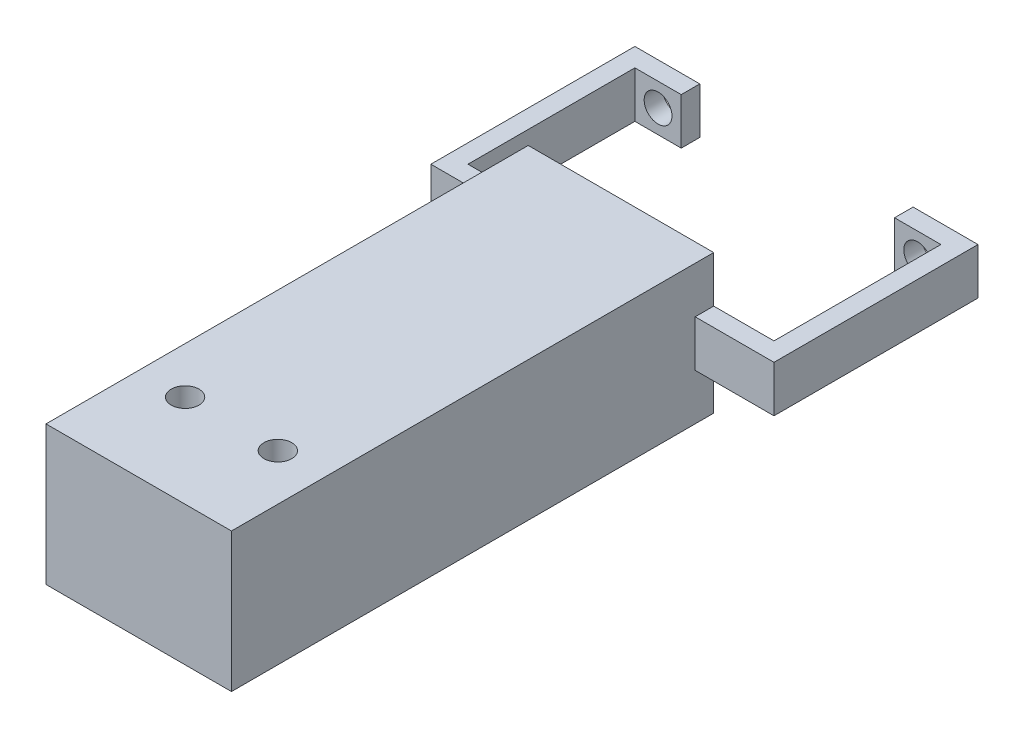
SolidWorks part; units mm, degrees
ref_plane "Спереди" through (0, 0, 0) normal (0, 0, 1) x (1, 0, 0)
ref_plane "Сверху" through (0, 0, 0) normal (0, 1, 0) x (1, 0, 0)
ref_plane "Справа" through (0, 0, 0) normal (1, 0, 0) x (0, 0, -1)
sketch "Эскиз1" plane through (0, 0, 0) normal (0, 0, 1) x (1, 0, 0)
  line L3 (11.5, 0) -> (11.5, 2.5)
  line L4 (11.5, 2.5) -> (16.5, 2.5)
  line L7 (11.5, -2.5) -> (11.5, 0)
  line L8 (11.5, -2.5) -> (16.5, -2.5)
  line L14 (-16.5, 2.5) -> (-18.5, 2.5)
  line L15 (-11.5, 0) -> (-11.5, 2.5)
  line L16 (-11.5, 2.5) -> (-16.5, 2.5)
  line L18 (-16.5, -2.5) -> (-11.5, -2.5)
  line L19 (-11.5, -2.5) -> (-11.5, 0)
  line L20 (-18.5, 2.5) -> (-18.5, -2.5)
  line L21 (-18.5, -2.5) -> (-16.5, -2.5)
  line L22 (16.5, -2.5) -> (18.5, -2.5)
  line L23 (18.5, -2.5) -> (18.5, 2.5)
  line L24 (18.5, 2.5) -> (16.5, 2.5)
  circle A0 centre (14, 0) radius 1.5
  circle A1 centre (-14, 0) radius 1.5
extrude "Бобышка-Вытянуть1" add sketch "Эскиз1" along normal blind 2
sketch "Эскиз3" plane through (0, 0, 2) normal (0, 0, 1) x (1, 0, 0)
  line L0 (-18.5, 2.5) -> (-16.5, 2.5)
  line L1 (-11.5, 2.5) -> (-18.5, 2.5) construction
  line L2 (-16.5, 2.5) -> (-16.5, -2.5)
  line L3 (-18.5, -2.5) -> (-11.5, -2.5) construction
  line L4 (-16.5, -2.5) -> (-18.5, -2.5)
  line L5 (-18.5, -2.5) -> (-18.5, 2.5)
  line L6 (18.5, -2.5) -> (16.5, -2.5)
  line L7 (11.5, -2.5) -> (18.5, -2.5) construction
  line L8 (16.5, -2.5) -> (16.5, 2.5)
  line L9 (18.5, 2.5) -> (11.5, 2.5) construction
  line L10 (16.5, 2.5) -> (18.5, 2.5)
  line L11 (18.5, 2.5) -> (18.5, -2.5)
extrude "Бобышка-Вытянуть2" add sketch "Эскиз3" along normal blind 18
sketch "Эскиз4" plane through (18.5, 0, 0) normal (1, 0, 0) x (0, 0, -1)
  line L0 (-20, -2.5) -> (-22, -2.5)
  line L1 (-22, -2.5) -> (-22, 2.5)
  line L2 (-22, 2.5) -> (-20, 2.5)
  line L3 (-20, -2.5) -> (-20, 2.5) construction
  line L4 (-20, 2.5) -> (-20, -2.5)
extrude "Бобышка-Вытянуть3" add sketch "Эскиз4" against normal blind 37
sketch "Эскиз5" plane through (0, 0, 22) normal (0, 0, 1) x (1, 0, 0)
  line L1 (-18.5, 2.5) -> (18.5, 2.5) construction
  line L2 (-10, 2.5) -> (-10, 7.5)
  line L3 (-10, 7.5) -> (10, 7.5)
  line L4 (10, 7.5) -> (10, -7.5)
  line L5 (10, -7.5) -> (-10, -7.5)
  line L6 (-10, -7.5) -> (-10, 2.5)
extrude "Бобышка-Вытянуть4" add sketch "Эскиз5" along normal blind 50 and the other way blind 2
sketch "Эскиз6" plane through (0, 7.5, 0) normal (0, 1, 0) x (1, 0, 0)
  line L0 (0, 0) -> (0, -88.9224) construction
  line L1 (0, -72) -> (0, -62) construction
  line L2 (10, -72) -> (-10, -72) construction
  line L3 (0, -62) -> (-5, -62) construction
  line L4 (0, -62) -> (5, -62) construction
  circle A0 centre (-5, -62) radius 1.5
  circle A1 centre (5, -62) radius 1.5
  dimension "D1" = 3
  dimension "D2" = 5
  dimension "D3" = 10
extrude "Вырез-Вытянуть1" cut sketch "Эскиз6" against normal through all contours A0 | A1
